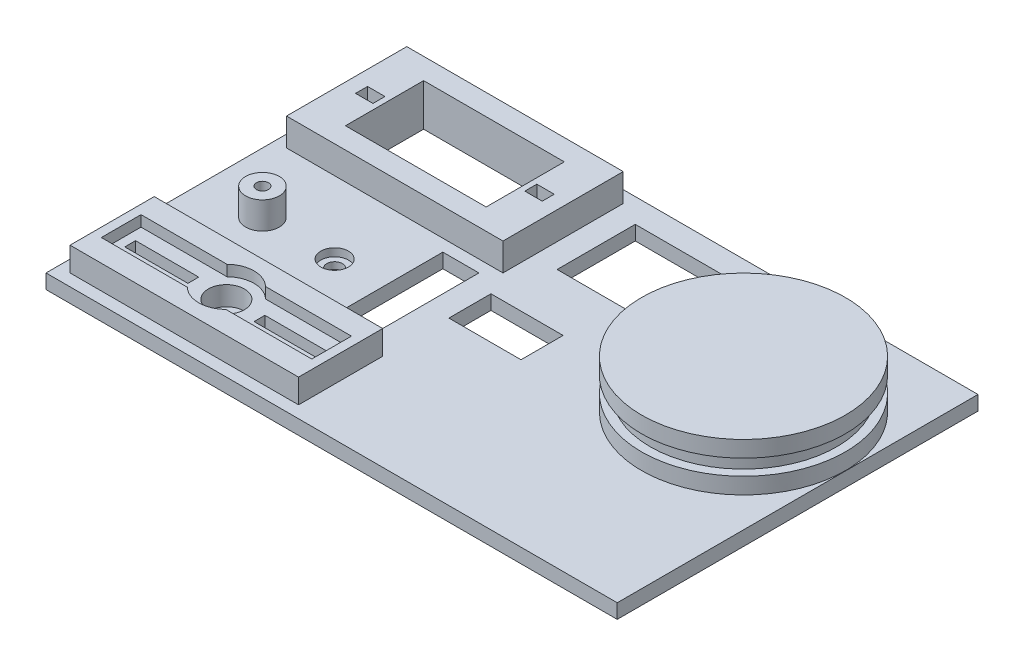
SolidWorks part; units mm, degrees
ref_plane "Front Plane" through (0, 0, 0) normal (0, 0, 1) x (1, 0, 0)
ref_plane "Top Plane" through (0, 0, 0) normal (0, 1, 0) x (1, 0, 0)
ref_plane "Right Plane" through (0, 0, 0) normal (1, 0, 0) x (0, 0, -1)
sketch "Sketch1" plane through (0, 0, 0) normal (0, 0, 1) x (1, 0, 0)
  line L1 (150, 0) -> (245, 0)
  line L2 (150, 0) -> (150, 2.4)
  line L3 (150, 2.4) -> (245, 2.4)
  line L4 (245, 0) -> (245, 2.4)
extrude "Boss-Extrude1" add sketch "Sketch1" along normal blind 60
sketch "Sketch2" plane through (0, 0, 0) normal (0, 0, 1) x (1, 0, 0)
  line L1 (152, 2.4) -> (188, 2.4)
  line L2 (152, 2.4) -> (152, 7)
  line L3 (152, 7) -> (188, 7)
  line L4 (188, 2.4) -> (188, 7)
extrude "Boss-Extrude2" add sketch "Sketch2" along normal blind 20 from offset 2
sketch "Sketch3" plane through (0, 0, 0) normal (0, 0, 1) x (1, 0, 0)
  line L1 (158.3, -1) -> (181.7, -1)
  line L2 (158.3, -1) -> (158.3, 8)
  line L3 (158.3, 8) -> (181.7, 8)
  line L4 (181.7, -1) -> (181.7, 8)
extrude "Boss-Extrude3" add sketch "Sketch3" along normal blind 13 from offset 5.5 separate body
combine bodies "Combine1" operation type subtract main body 102 bodies to subtract 103
sketch "Sketch4" plane through (0, 0, 0) normal (0, 0, 1) x (1, 0, 0)
  line L1 (154.475, -1) -> (157.375, -1)
  line L2 (154.475, -1) -> (154.475, 8)
  line L3 (154.475, 8) -> (157.375, 8)
  line L4 (157.375, -1) -> (157.375, 8)
extrude "Boss-Extrude4" add sketch "Sketch4" along normal blind 2 from offset 11 separate body
combine bodies "Combine2" operation type subtract main body 104 bodies to subtract 105
sketch "Sketch5" plane through (0, 0, 0) normal (0, 0, 1) x (1, 0, 0)
  line L1 (182.625, -1) -> (185.525, -1)
  line L2 (182.625, -1) -> (182.625, 8)
  line L3 (182.625, 8) -> (185.525, 8)
  line L4 (185.525, -1) -> (185.525, 8)
extrude "Boss-Extrude5" add sketch "Sketch5" along normal blind 2 from offset 11 separate body
combine bodies "Combine3" operation type subtract main body 106 bodies to subtract 107
sketch "Sketch6" plane through (0, 0, 0) normal (0, 0, 1) x (1, 0, 0)
  line L1 (192, -1) -> (211.4, -1)
  line L2 (192, -1) -> (192, 3.4)
  line L3 (192, 3.4) -> (211.4, 3.4)
  line L4 (211.4, -1) -> (211.4, 3.4)
extrude "Boss-Extrude6" add sketch "Sketch6" along normal blind 13 from offset 4 separate body
combine bodies "Combine4" operation type subtract main body 108 bodies to subtract 109
sketch "Sketch7" plane through (0, 0, 0) normal (0, 1, 0) x (1, 0, 0)
  circle A0 centre (160, -34) radius 2.8
extrude "Boss-Extrude7" add sketch "Sketch7" along normal blind 4.5 from offset 2.4
sketch "Sketch8" plane through (0, 0, 0) normal (0, 1, 0) x (1, 0, 0)
  circle A0 centre (160, -34) radius 1
extrude "Boss-Extrude8" add sketch "Sketch8" along normal blind 6.3 from offset 1.6 separate body
combine bodies "Combine5" operation type subtract main body 111 bodies to subtract 112
sketch "Sketch9" plane through (0, 0, 0) normal (0, 1, 0) x (1, 0, 0)
  circle A0 centre (172, -34) radius 1.3
extrude "Boss-Extrude9" add sketch "Sketch9" along normal blind 4.4 from offset 1 separate body offset against normal yes
combine bodies "Combine6" operation type subtract main body 113 bodies to subtract 114
sketch "Sketch10" plane through (0, 0, 0) normal (0, 1, 0) x (1, 0, 0)
  circle A0 centre (172, -34) radius 2.3
extrude "Boss-Extrude10" add sketch "Sketch10" along normal blind 2.3 from offset 1.1 separate body
combine bodies "Combine7" operation type subtract main body 115 bodies to subtract 116
sketch "Sketch11" plane through (0, 0, 0) normal (0, 0, 1) x (1, 0, 0)
  line L1 (180, -1) -> (186, -1)
  line L2 (180, -1) -> (180, 3.4)
  line L3 (180, 3.4) -> (186, 3.4)
  line L4 (186, -1) -> (186, 3.4)
extrude "Boss-Extrude11" add sketch "Sketch11" along normal blind 17 from offset 24 separate body
combine bodies "Combine8" operation type subtract main body 117 bodies to subtract 118
sketch "Sketch12" plane through (0, 0, 0) normal (0, 0, 1) x (1, 0, 0)
  line L1 (190, -1) -> (202, -1)
  line L2 (190, -1) -> (190, 3.4)
  line L3 (190, 3.4) -> (202, 3.4)
  line L4 (202, -1) -> (202, 3.4)
extrude "Boss-Extrude12" add sketch "Sketch12" along normal blind 7 from offset 26 separate body
combine bodies "Combine9" operation type subtract main body 119 bodies to subtract 120
sketch "Sketch13" plane through (0, 0, 0) normal (0, 1, 0) x (1, 0, 0)
  circle A0 centre (228, -22) radius 16.95
extrude "Boss-Extrude13" add sketch "Sketch13" along normal blind 8 from offset 2.4
sketch "Sketch14" plane through (0, 0, 0) normal (0, 1, 0) x (1, 0, 0)
  circle A0 centre (228, -22) radius 20
extrude "Boss-Extrude14" add sketch "Sketch14" along normal blind 2.6 from offset 5.1 separate body
combine bodies "Combine10" operation type subtract main body 122 bodies to subtract 123
sketch "Sketch15" plane through (0, 0, 0) normal (0, 1, 0) x (1, 0, 0)
  circle A0 centre (228, -22) radius 15.5
extrude "Boss-Extrude15" add sketch "Sketch15" along normal blind 2.6 from offset 5.1
sketch "Sketch16" plane through (0, 0, 0) normal (0, 0, 1) x (1, 0, 0)
  line L1 (152, 2.4) -> (190, 2.4)
  line L2 (152, 2.4) -> (152, 6.4)
  line L3 (152, 6.4) -> (190, 6.4)
  line L4 (190, 2.4) -> (190, 6.4)
extrude "Boss-Extrude16" add sketch "Sketch16" along normal blind 14 from offset 44
sketch "Sketch17" plane through (0, 0, 0) normal (0, 1, 0) x (1, 0, 0)
  circle A0 centre (171, -51) radius 4.6
extrude "Boss-Extrude17" add sketch "Sketch17" along normal blind 2.3 from offset 4.6 separate body
combine bodies "Combine11" operation type subtract main body 127 bodies to subtract 128
sketch "Sketch18" plane through (0, 0, 0) normal (0, 0, 1) x (1, 0, 0)
  line L1 (171, 4.6) -> (188.5, 4.6)
  line L2 (171, 4.6) -> (171, 6.9)
  line L3 (171, 6.9) -> (188.5, 6.9)
  line L4 (188.5, 4.6) -> (188.5, 6.9)
extrude "Boss-Extrude18" add sketch "Sketch18" along normal blind 6.6 from offset 47.7 separate body
combine bodies "Combine12" operation type subtract main body 129 bodies to subtract 130
sketch "Sketch19" plane through (0, 0, 0) normal (0, 0, 1) x (1, 0, 0)
  line L1 (176.5, 1.4) -> (187, 1.4)
  line L2 (176.5, 1.4) -> (176.5, 7.4)
  line L3 (176.5, 7.4) -> (187, 7.4)
  line L4 (187, 1.4) -> (187, 7.4)
extrude "Boss-Extrude19" add sketch "Sketch19" along normal blind 1.8 from offset 50.1 separate body
combine bodies "Combine13" operation type subtract main body 131 bodies to subtract 132
sketch "Sketch20" plane through (0, 0, 0) normal (0, 0, 1) x (1, 0, 0)
  line L1 (153.5, 4.6) -> (171, 4.6)
  line L2 (153.5, 4.6) -> (153.5, 6.9)
  line L3 (153.5, 6.9) -> (171, 6.9)
  line L4 (171, 4.6) -> (171, 6.9)
extrude "Boss-Extrude20" add sketch "Sketch20" along normal blind 6.6 from offset 47.7 separate body
combine bodies "Combine14" operation type subtract main body 133 bodies to subtract 134
sketch "Sketch21" plane through (0, 0, 0) normal (0, 0, 1) x (1, 0, 0)
  line L1 (155, 1.4) -> (165.5, 1.4)
  line L2 (155, 1.4) -> (155, 7.4)
  line L3 (155, 7.4) -> (165.5, 7.4)
  line L4 (165.5, 1.4) -> (165.5, 7.4)
extrude "Boss-Extrude21" add sketch "Sketch21" along normal blind 1.8 from offset 50.1 separate body
combine bodies "Combine15" operation type subtract main body 135 bodies to subtract 136
sketch "Sketch22" plane through (0, 0, 0) normal (0, 1, 0) x (1, 0, 0)
  circle A0 centre (171, -51) radius 3
extrude "Boss-Extrude22" add sketch "Sketch22" along normal blind 6 from offset 1.4 separate body
combine bodies "Combine16" operation type subtract main body 137 bodies to subtract 138
